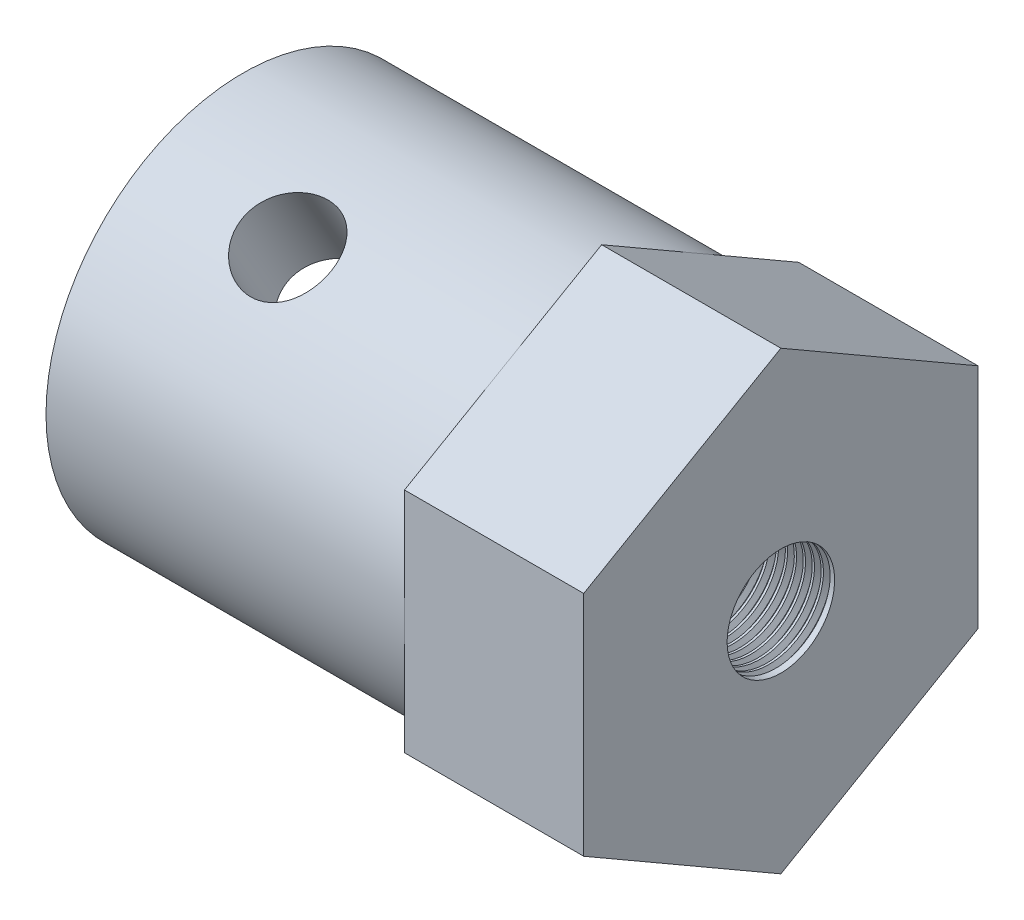
SolidWorks part; units mm, degrees
material "Copper"
ref_plane "Front Plane" through (0, 0, 0) normal (0, 0, 1) x (1, 0, 0)
ref_plane "Top Plane" through (0, 0, 0) normal (0, 1, 0) x (1, 0, 0)
ref_plane "Right Plane" through (0, 0, 0) normal (1, 0, 0) x (0, 0, -1)
other "Center of Mass"
sketch "Sketch1" plane through (0, 0, 0) normal (0, 0, 1) x (1, 0, 0)
  line L0 (-36.6423, 0) -> (-21.9859, 0) construction
  line L1 (-21.2877, 1.5) -> (-21.2877, 3)
  line L2 (-21.2877, 3) -> (-33.2877, 3)
  line L3 (-33.2877, 3) -> (-33.2877, 5.5)
  line L4 (-33.2877, 5.5) -> (-23.2877, 5.5)
  line L5 (-23.2877, 5.5) -> (-23.2877, 6.35)
  line L6 (-23.2877, 6.35) -> (-18.2877, 6.35)
  line L7 (-18.2877, 6.35) -> (-18.2877, 1.5)
  line L8 (-18.2877, 1.5) -> (-21.2877, 1.5)
  dimension "D1" = 12.7
  dimension "D2" = 3
  dimension "D3" = 5
  dimension "D4" = 12
  dimension "D5" = 10
  dimension "D6" = 6
  dimension "D7" = 11
revolve "Revolve1" add sketch "Sketch1" angle 360 about L0
sketch "Sketch2" plane through (-18.2877, 0, 0) normal (1, 0, 0) x (0, 0, -1)
  line L1 (0, 6.35) -> (-5.4993, 3.175)
  line L2 (-5.4993, 3.175) -> (-5.4993, -3.175)
  line L3 (-5.4993, -3.175) -> (0, -6.35)
  line L4 (0, -6.35) -> (5.4993, -3.175)
  line L5 (5.4993, -3.175) -> (5.4993, 3.175)
  line L6 (5.4993, 3.175) -> (0, 6.35)
  circle A0 centre (0, 0) radius 5.4993 construction
  dimension "D1" = 10.9985
extrude "Cut-Extrude1" cut sketch "Sketch2" against normal up to surface (5 mm away) flip side to cut up to face at (-23.2877, 0, 5.5)
thread "Thread1" pitch 0.25 method cut profile "Thread Profile1" start angle 0, offset 0, length 0, pitch 0.25, diameter 3
ref_plane "Plane1" through (-18.2877, 0, 1.5) normal (0, -1, 0) x (0, 0, 1)
sketch "Thread Profile1" plane through (-18.2877, 0, 1.5) normal (0, -1, 0) x (0, 0, 1)
  line L0 (0, 0) -> (0, 0.25) construction
  line L1 (0, 0) -> (0.1353, 0.0781)
  line L2 (0.1353, 0.0781) -> (0.1353, 0.1094)
  line L3 (0.1353, 0.1094) -> (0, 0.1875)
  line L4 (0.1353, 0.0937) -> (0, 0.0937) construction
  line L11 (0, 0) -> (0, 0.1875)
  point P2 (0, 0)
  dimension "Pitch" = 0.25
  dimension "Profile_Angle" = 60
  dimension "Profile_Land" = 0.0312
  dimension "Profile_Height" = 0.1353
ref_plane "Plane2" through (0, 6.4946, 3.7496) normal (0, 0.866, 0.5) x (1, 0, 0)
sketch "Sketch14" plane through (0, 6.4946, 3.7496) normal (0, 0.866, 0.5) x (1, 0, 0)
  line L0 (-35.8299, 0) -> (-16.8525, 0) construction
  line L1 (-29.2877, 2.6497) -> (-29.2877, -2.7316) construction
  line L2 (-33.2877, 5.5) -> (-33.2877, -5.5) construction
  dimension "D1" = 4
hole_wizard "M3x0.5 Tapped Hole3" positions "Sketch15" profile "Sketch16" tap size "M3x0.5" standard "ANSI Metric"
sketch "Sketch15" plane through (0, 6.4946, 3.7496) normal (0, 0.866, 0.5) x (1, 0, 0)
  line L0 (-29.2877, 2.6497) -> (-29.2877, -2.7316) construction
  point P0 (-29.2877, -0.041)
sketch "Sketch16" plane through (-29.2877, 6.4741, 3.7851) normal (1, 0, 0) x (0, -0.5, 0.866)
  line L0 (0, 0) -> (0, 8.2511)
  line L1 (0, 8.2511) -> (1.25, 7.5)
  line L2 (1.25, 7.5) -> (1.25, 0)
  line L5 (1.25, 0) -> (0, 0)
  line L10 (0, 8.2511) -> (-1.25, 7.5) construction
  line L11 (0, -6.35) -> (0, 107.95) construction
  dimension "Tap Drill Dia." = 2.5
  dimension "Tap Drill Depth" = 7.5
  dimension "Drill Angle" = 118
cosmetic thread "Hole Thread4" parameters "D1"=4.7912, "D2"=3
